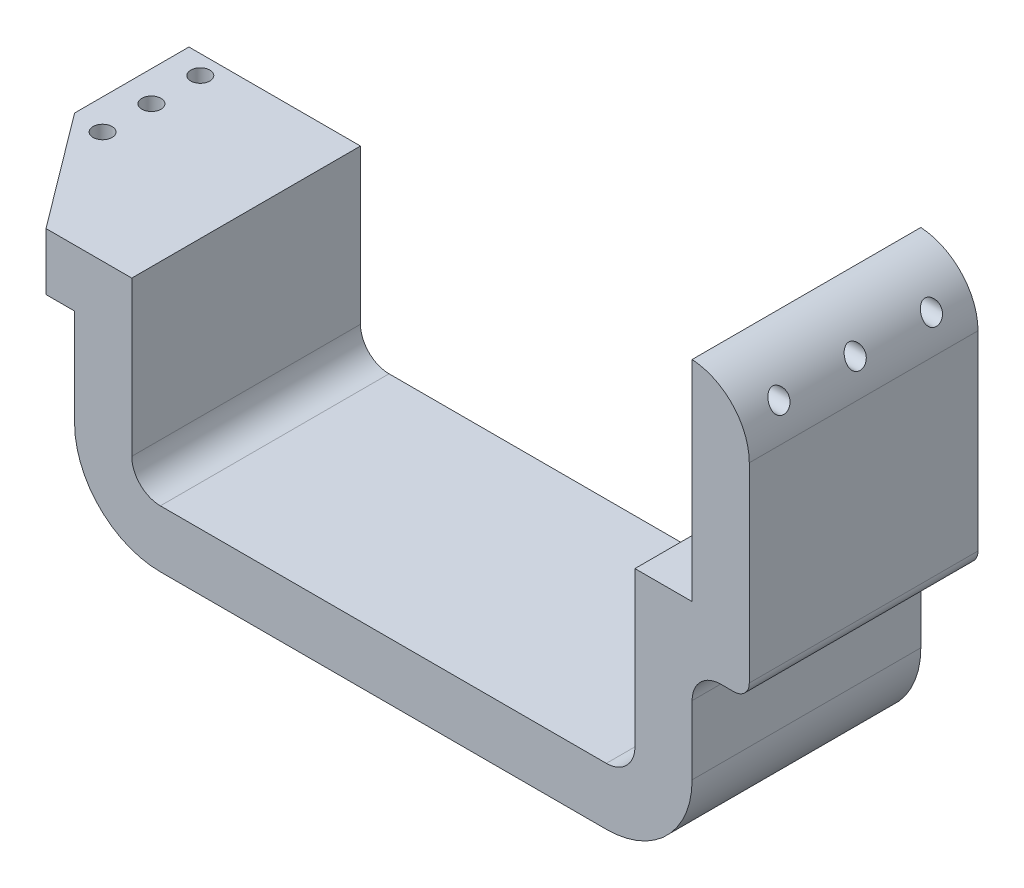
SolidWorks part; units mm, degrees
ref_plane "Front Plane" through (0, 0, 0) normal (0, 0, 1) x (1, 0, 0)
ref_plane "Top Plane" through (0, 0, 0) normal (0, 1, 0) x (1, 0, 0)
ref_plane "Right Plane" through (0, 0, 0) normal (1, 0, 0) x (0, 0, -1)
sketch "Sketch1" plane through (0, 0, 0) normal (0, 0, 1) x (1, 0, 0)
  line L0 (-40.64, 12.7) -> (-50.165, 12.7) construction
  line L1 (-38.1, -12.7) -> (38.1, -12.7) construction
  line L2 (-38.1, -12.7) -> (-38.1, 12.7) construction
  line L3 (-38.1, 12.7) -> (38.1, 12.7) construction
  line L4 (38.1, -12.7) -> (38.1, 12.7) construction
  line L5 (-38.1, -12.7) -> (38.1, 12.7) construction
  line L6 (-38.1, 12.7) -> (38.1, -12.7) construction
  line L7 (-40.64, 12.7) -> (-40.64, -13.0175) construction
  line L8 (43.18, 12.7) -> (52.705, 12.7) construction
  line L9 (52.705, 12.7) -> (52.705, 22.225) construction
  line L10 (52.705, 22.225) -> (62.23, 22.225) construction
  line L11 (-35.8775, -17.78) -> (38.4175, -17.78) construction
  line L12 (43.18, -13.0175) -> (43.18, 12.7) construction
  line L13 (-50.165, 12.7) -> (-50.165, -13.0175) construction
  line L14 (-35.8775, -27.305) -> (38.4175, -27.305)
  line L15 (52.705, -13.0175) -> (52.705, -1.5875) construction
  line L16 (57.4675, 3.175) -> (62.23, 3.175) construction
  line L17 (62.23, 3.175) -> (62.23, 22.225) construction
  line L18 (52.705, -13.0175) -> (52.705, 3.175) construction
  line L19 (52.705, 3.175) -> (62.23, 3.175) construction
  line L20 (-50.165, -13.0175) -> (-50.165, 12.7) construction
  line L21 (-50.165, 12.7) -> (-40.64, 12.7)
  line L22 (-40.64, 12.7) -> (-40.64, -13.0175)
  line L23 (-35.8775, -17.78) -> (38.4175, -17.78)
  line L24 (43.18, -13.0175) -> (43.18, 12.7)
  line L25 (43.18, 12.7) -> (52.705, 12.7)
  line L29 (57.4675, 3.175) -> (62.23, 3.175)
  line L30 (52.705, -1.5875) -> (52.705, -13.0175)
  line L34 (-50.165, 3.175) -> (-50.165, -13.0175)
  line L35 (-50.165, 12.7) -> (-59.69, 12.7)
  line L36 (-59.69, 12.7) -> (-69.215, 12.7)
  line L37 (-69.215, 12.7) -> (-69.215, 3.175)
  line L38 (-69.215, 3.175) -> (-50.165, 3.175)
  line L39 (52.705, 12.7) -> (52.705, 47.625)
  line L40 (52.705, 47.625) -> (62.23, 47.625)
  line L41 (62.23, 47.625) -> (62.23, 3.175)
  arc A0 (-40.64, -13.0175) -> (-35.8775, -17.78) centre (-35.8775, -13.0175) ccw construction
  arc A1 (38.4175, -17.78) -> (43.18, -13.0175) centre (38.4175, -13.0175) ccw construction
  arc A2 (-50.165, -13.0175) -> (-35.8775, -27.305) centre (-35.8775, -13.0175) ccw
  arc A3 (38.4175, -27.305) -> (52.705, -13.0175) centre (38.4175, -13.0175) ccw
  arc A4 (52.705, -1.5875) -> (57.4675, 3.175) centre (57.4675, -1.5875) cw construction
  arc A5 (-40.64, -13.0175) -> (-35.8775, -17.78) centre (-35.8775, -13.0175) ccw
  arc A6 (38.4175, -17.78) -> (43.18, -13.0175) centre (38.4175, -13.0175) ccw
  arc A7 (52.705, -1.5875) -> (57.4675, 3.175) centre (57.4675, -1.5875) cw
  point P0 (0, 0)
  dimension "D7" = 4.7625
  dimension "D9" = 25.4
  dimension "D1" = 76.2
  dimension "D2" = 25.4
  dimension "D3" = 9.525
  dimension "D4" = 2.54
  dimension "D5" = 5.08
  dimension "D6" = 5.08
  dimension "D8" = 9.525
extrude "Boss-Extrude1" add sketch "Sketch1" along normal blind 38.1
fillet "Fillet1" radius 2.54 1 edges at (62.23, 3.175, 19.05)
fillet "Fillet2" radius 10.16 2 edges at (-69.215, 3.175, 19.05) (62.23, 47.625, 19.05)
sketch "Sketch2" plane through (0, 3.175, 0) normal (0, -1, 0) x (1, 0, 0)
  line L1 (-50.165, 44.45) -> (-50.165, 19.05) construction
  line L2 (-50.165, 38.1) -> (-50.165, 0) construction
  line L3 (-50.165, 19.05) -> (-69.215, 19.05) construction
  line L4 (-35.8775, 0) -> (38.4175, 0) construction
  line L5 (-69.215, 19.05) -> (-69.215, 44.45)
  line L6 (-69.215, 44.45) -> (-50.165, 44.45)
  line L9 (-69.215, 19.05) -> (-50.165, 44.45)
  dimension "D1" = 19.05
  dimension "D2" = 25.4
  dimension "D3" = 19.05
extrude "Cut-Extrude2" cut sketch "Sketch2" against normal through all
sketch "Sketch3" plane through (0, 3.175, 0) normal (0, -1, 0) x (1, 0, 0)
  line L0 (-64.1449, 0) -> (-64.1449, 25.8101) construction
  line L1 (-69.215, 0) -> (-59.0749, 0) construction
  line L2 (-59.0749, 32.5702) -> (-69.215, 19.05) construction
  circle A0 centre (-64.1449, 3.175) radius 1.5875
  circle A1 centre (-64.1449, 11.3175) radius 1.5875
  circle A2 centre (-64.1449, 19.4601) radius 1.5875
  dimension "D1" = 3.175
  dimension "D2" = 3.175
  dimension "D4" = 6.35
  dimension "D3" = 3
extrude "Cut-Extrude3" cut sketch "Sketch3" against normal through all
sketch "Sketch4" plane through (62.23, 0, 0) normal (1, 0, 0) x (0, 0, -1)
  line L0 (-38.1, 42.5549) -> (0, 42.5549) construction
  line L1 (-38.1, 47.625) -> (-38.1, 37.4849) construction
  line L2 (0, 37.4849) -> (0, 47.625) construction
  circle A0 centre (-6.35, 42.5549) radius 1.5875
  circle A1 centre (-19.05, 42.5549) radius 1.5875
  circle A2 centre (-31.75, 42.5549) radius 1.5875
  dimension "D1" = 3.175
  dimension "D2" = 6.35
  dimension "D4" = 6.35
  dimension "D3" = 3
extrude "Cut-Extrude4" cut sketch "Sketch4" against normal through all
